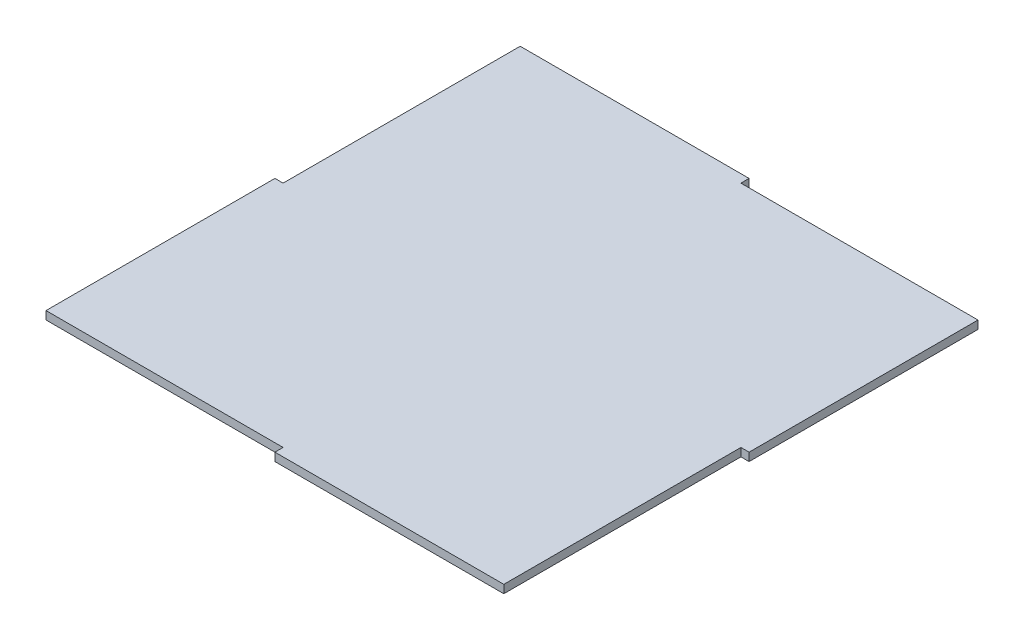
SolidWorks part; units mm, degrees
material "Acrylic (Medium-high impact)"
ref_plane "Front Plane" through (0, 0, 0) normal (0, 0, 1) x (1, 0, 0)
ref_plane "Top Plane" through (0, 0, 0) normal (0, 1, 0) x (1, 0, 0)
ref_plane "Right Plane" through (0, 0, 0) normal (1, 0, 0) x (0, 0, -1)
sketch "Sketch1" plane through (0, 0, 0) normal (0, 1, 0) x (1, 0, 0)
  line L0 (-112.5062, 93.3127) -> (-112.5062, 96.4877)
  line L1 (-112.5062, 93.3127) -> (65.2938, 93.3127)
  line L2 (-112.5062, 93.3127) -> (-112.5062, -84.4873)
  line L3 (-112.5062, -84.4873) -> (65.2938, -84.4873)
  line L4 (65.2938, 93.3127) -> (65.2938, -84.4873)
  line L5 (-112.5062, 96.4877) -> (-23.6062, 96.4877)
  line L6 (-23.6062, 96.4877) -> (-23.6062, 93.3127)
  line L7 (-112.5062, -84.4873) -> (-115.6812, -84.4873)
  line L8 (-115.6812, -84.4873) -> (-115.6812, 4.4127)
  line L9 (-115.6812, 4.4127) -> (-112.5062, 4.4127)
  line L10 (65.2938, -84.4873) -> (65.2938, -87.6623)
  line L11 (65.2938, -87.6623) -> (-23.6062, -87.6623)
  line L12 (-23.6062, -87.6623) -> (-23.6062, -84.4873)
  line L13 (65.2938, 93.3127) -> (68.4688, 93.3127)
  line L14 (68.4688, 93.3127) -> (68.4688, 4.4127)
  line L15 (68.4688, 4.4127) -> (65.2938, 4.4127)
  point P4 (-23.6062, 93.3127)
  point P5 (-112.5062, 4.4127)
  point P9 (65.2938, 4.4127)
  point P10 (-23.6062, -84.4873)
  dimension "D1" = 177.8
  dimension "D2" = 177.8
  dimension "D3" = 3.175
  dimension "D4" = 3.175
  dimension "D5" = 3.175
  dimension "D6" = 3.175
extrude "Boss-Extrude1" add sketch "Sketch1" along normal blind 3.175 contours L9 L8 L7 L2 | L6 L5 L0 L1 | L4 L1 L2 L3 | L15 L14 L13 L4 | L12 L11 L10 L3 region at (-68.0562, 0, -94.9002) region at (-23.6062, 0, -4.4127) region at (-114.0937, 0, 40.0373) region at (66.8813, 0, -48.8627) region at (20.8438, 0, 86.0748)
